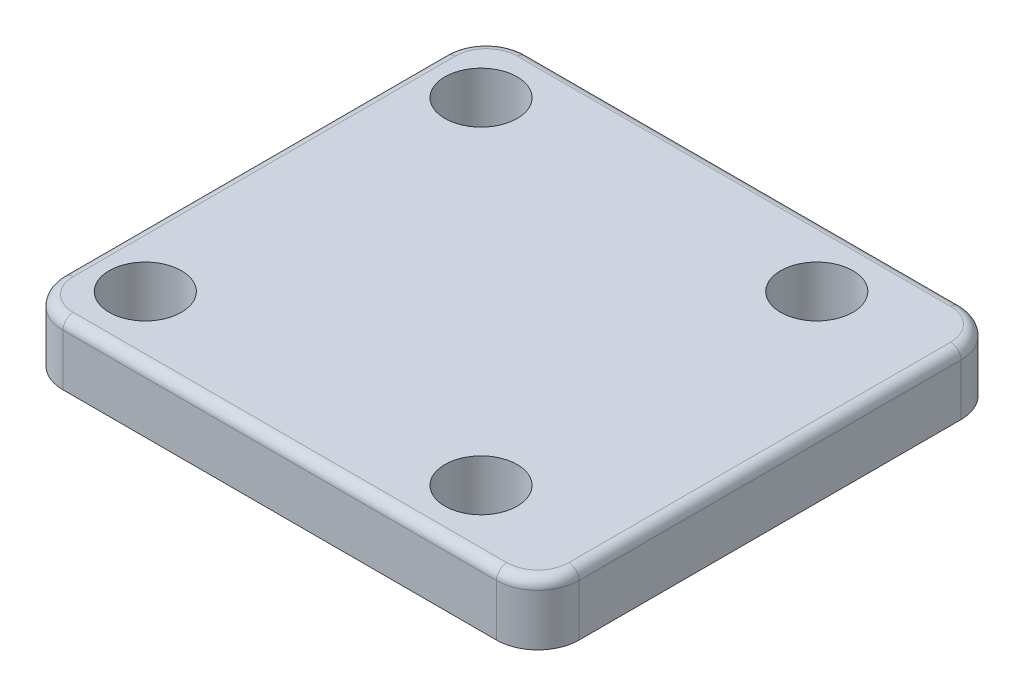
SolidWorks part; units mm, degrees
material "6061 Alloy"
ref_plane "Front Plane" through (0, 0, 0) normal (0, 0, 1) x (1, 0, 0)
ref_plane "Top Plane" through (0, 0, 0) normal (0, 1, 0) x (1, 0, 0)
ref_plane "Right Plane" through (0, 0, 0) normal (1, 0, 0) x (0, 0, -1)
sketch "Sketch1" plane through (0, 0, 0) normal (0, 1, 0) x (1, 0, 0)
  line L1 (-10.5, -11.25) -> (10.5, -11.25)
  line L2 (-12.5, -9.25) -> (-12.5, 9.25)
  line L3 (-10.5, 11.25) -> (10.5, 11.25)
  line L4 (12.5, -9.25) -> (12.5, 9.25)
  line L5 (-12.5, -11.25) -> (12.5, 11.25) construction
  line L6 (-12.5, 11.25) -> (12.5, -11.25) construction
  arc A0 (12.5, -9.25) -> (10.5, -11.25) centre (10.5, -9.25) cw
  arc A1 (-10.5, -11.25) -> (-12.5, -9.25) centre (-10.5, -9.25) cw
  arc A2 (12.5, 9.25) -> (10.5, 11.25) centre (10.5, 9.25) ccw
  arc A3 (-12.5, 9.25) -> (-10.5, 11.25) centre (-10.5, 9.25) cw
  point P0 (0, 0)
  dimension "D3" = 2
  dimension "D1" = 22.5
  dimension "D2" = 25
extrude "Boss-Extrude1" add sketch "Sketch1" along normal blind 3
fillet "Fillet1" radius 0.5 8 edges at (0, 3, 11.25) (-11.9142, 3, 10.6642) (-12.5, 3, 0) (-11.9142, 3, -10.6642) (0, 3, -11.25) (11.9142, 3, -10.6642) (12.5, 3, 0) (11.9142, 3, 10.6642)
sketch "Sketch2" plane through (0, 0, 0) normal (0, -1, 0) x (1, 0, 0)
  line L0 (-12.5, -9.25) -> (-12.5, 9.25) construction
  circle A0 centre (-1.5, 0) radius 8
  dimension "D1" = 16
  dimension "D2" = 11
  dimension "D3" = 1.5
extrude "Boss-Extrude2" add sketch "Sketch2" along normal blind 0.5
sketch "Sketch3" plane through (0, -0.5, 0) normal (0, -1, 0) x (-1, 0, 0)
  circle A0 centre (1.5, 0) radius 7.5
  circle A1 centre (1.5, 0) radius 8 construction
  dimension "D1" = 0.5
extrude "Boss-Extrude3" add sketch "Sketch3" along normal blind 0.5
fillet "Fillet2" radius 0.5 1 edges at (-1.5, -0.5, -7.5) profile chamfer first distance on face at (-1.5, -0.5, -7.5)
sketch "Sketch5" plane through (0, 0, 0) normal (0, -1, 0) x (-1, 0, 0)
  line L0 (11.5, 10) -> (-8.5, -10) construction
  line L2 (1.5, 4.7757) -> (1.5, -8.8901) construction
  line L3 (-4.085, 0) -> (8.1701, 0) construction
  line L5 (-7.7021, 9.2021) -> (10.5, -9) construction
  circle A0 centre (1.5, 0) radius 11.5 construction
  circle A2 centre (9.6317, 8.1317) radius 1.75
  circle A3 centre (1.5, 0) radius 7.5 construction
  dimension "D1" = 23
  dimension "D2" = 3.5
  dimension "D4" = 8.8901
  dimension "D5" = 4.7757
  dimension "D6" = 6.6701
  dimension "D7" = 5.585
  dimension "D8" = 45
  dimension "D9" = 45
  dimension "D10" = 12
  dimension "D11" = 10
  dimension "D12" = 9
  dimension "D13" = 10
extrude "Cut-Extrude2" cut sketch "Sketch5" against normal blind 10 contours A2
pattern_circular "CirPattern2" count 4 over 360 about axis through (-1.5, 0, 0) along (0, -1, 0) of "Cut-Extrude2"
